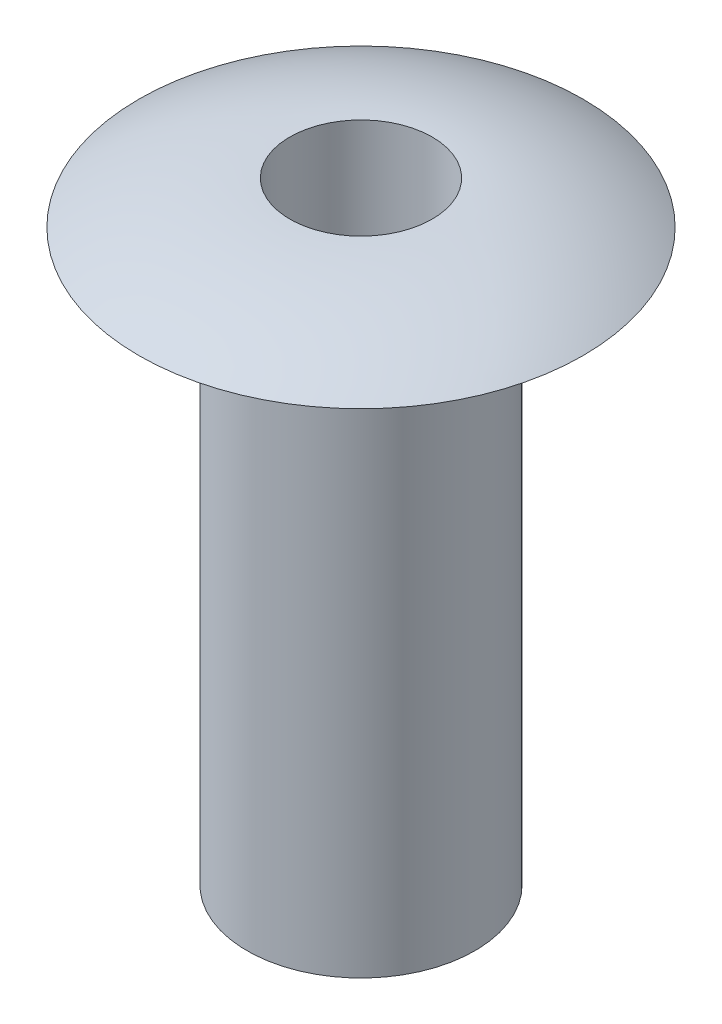
SolidWorks part; units mm, degrees
material "AISI 316 Arkusz stali nierdzewnej (SS)"
ref_plane "Płaszczyzna przednia" through (0, 0, 0) normal (0, 0, 1) x (1, 0, 0)
ref_plane "Płaszczyzna górna" through (0, 0, 0) normal (0, 1, 0) x (1, 0, 0)
ref_plane "Płaszczyzna prawa" through (0, 0, 0) normal (1, 0, 0) x (0, 0, -1)
sketch "Szkic1" plane through (0, 0, 0) normal (0, 0, 1) x (1, 0, 0)
  line L0 (0, 0) -> (0, 15.059) construction
  line L1 (-1.25, 10.75) -> (-1.25, 0)
  line L2 (-1.25, 0) -> (-2, 0)
  line L3 (-2, 0) -> (-2, 10)
  line L4 (-2, 10) -> (-3.9, 10)
  arc A0 (-1.25, 10.75) -> (-3.9, 10) centre (-1.25, 5.6933) ccw
  dimension "D5" = 10
  dimension "D1" = 4
  dimension "D2" = 2.5
  dimension "D3" = 7.8
  dimension "D4" = 0.75
revolve "Obrót1" add sketch "Szkic1" angle 360 about L0
